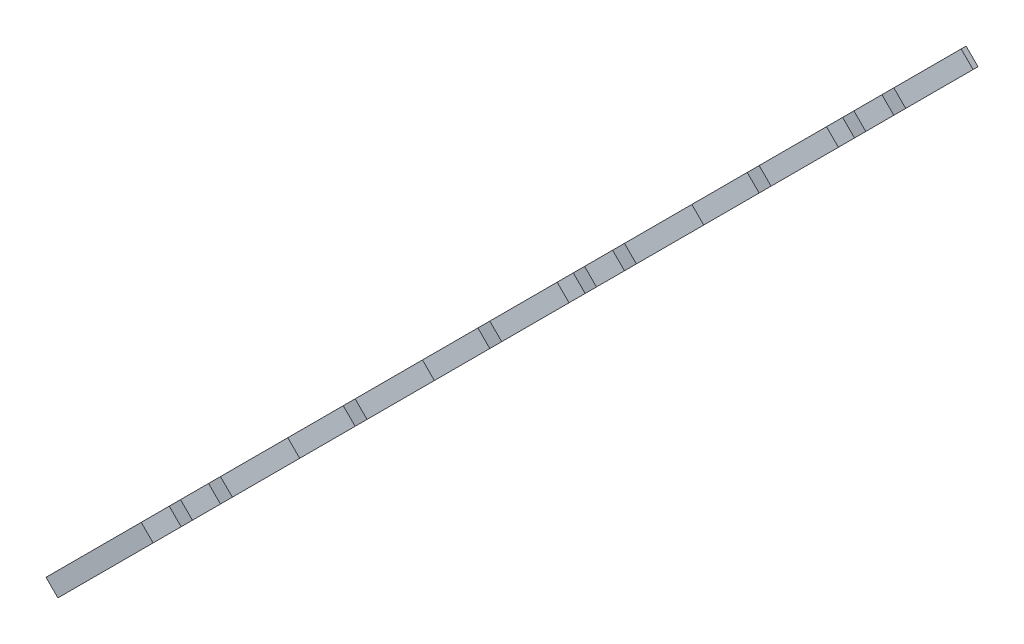
SolidWorks part; units mm, degrees
ref_plane "Front Plane" through (0, 0, 0) normal (0, 0, 1) x (1, 0, 0)
ref_plane "Top Plane" through (0, 0, 0) normal (0, 1, 0) x (1, 0, 0)
ref_plane "Right Plane" through (0, 0, 0) normal (1, 0, 0) x (0, 0, -1)
sketch "Sketch1" plane through (0, 0, 0) normal (0, 0, 1) x (1, 0, 0)
  line L0 (91.6648, 29.3027) -> (52.5461, -9.816) construction
  line L2 (78.5772, 20.7053) -> (74.1015, 16.2295) construction
  line L3 (78.5917, 11.7394) -> (83.0674, 16.2151) construction
  line L4 (37.7171, 7.6839) -> (33.2269, 12.174)
  line L5 (37.7171, 7.6839) -> (73.6381, 43.6049)
  line L6 (33.2269, 12.174) -> (69.148, 48.095)
  line L7 (73.6381, 43.6049) -> (69.148, 48.095)
  line L8 (110.4572, 6.7859) -> (74.5361, -29.1352) construction
  line L9 (74.5361, -29.1352) -> (70.046, -24.645) construction
  line L10 (105.967, 11.276) -> (70.046, -24.645) construction
extrude "Boss-Extrude1" add sketch "Sketch1" along normal up to surface (304.8 mm away)
sketch "Sketch2" plane through (58.6215, 58.6215, 0) normal (0.7071, 0.7071, 0) x (0, 0, -1)
  line L0 (-304.8, -21.2367) -> (0, -21.2367) construction
  line L1 (-279.4, -21.2367) -> (-254, -21.2367)
  line L2 (-279.4, -21.2367) -> (-279.4, -14.8867)
  line L3 (-279.4, -14.8867) -> (-254, -14.8867)
  line L4 (-254, -21.2367) -> (-254, -14.8867)
  line L5 (-304.8, -14.8867) -> (0, -14.8867) construction
  dimension "D1" = 25.4
  dimension "D2" = 25.4
extrude "Boss-Extrude2" add sketch "Sketch2" along normal blind 6.35
pattern_linear "LPattern1" count 6 spacing 50.8 along (0, 0, -1) of "Boss-Extrude2"
sketch "Sketch3" plane through (15.0166, -15.0166, 0) normal (0.7071, -0.7071, 0) x (0, 0, -1)
  circle A0 centre (-273.3375, 57.5033) radius 2.8702
extrude "Cut-Extrude1" cut sketch "Sketch3" against normal up to surface (6.35 mm away) up to face at (68.6299, 47.5769, 155.3308)
sketch "Sketch4" plane through (0, 0, 0) normal (0, 0, -1) x (-1, 0, 0)
  line L0 (-33.2269, 12.174) -> (-37.7171, 7.6839)
  line L1 (-73.6381, 52.5852) -> (-33.2269, 12.174) construction
  line L2 (-37.7171, 7.6839) -> (-78.1282, 48.095) construction
  line L3 (-37.7171, 7.6839) -> (-46.6973, 16.6641)
  line L4 (-46.6973, 16.6641) -> (-42.2072, 21.1543)
  line L5 (-42.2072, 21.1543) -> (-33.2269, 12.174)
  dimension "D1" = 12.7
  dimension "D2" = 0
  dimension "D3" = 6.35
extrude "Boss-Extrude3" add sketch "Sketch4" along normal blind 6.35
pattern_linear "LPattern2" count 2 spacing 38.1 along (0.7071, 0.7071, 0) of "Boss-Extrude3"
sketch "Sketch5" plane through (10.5265, -10.5265, 0) normal (-0.7071, 0.7071, 0) x (0.7071, 0.7071, 0)
  line L0 (57.5033, -7.2251) -> (57.5033, -39.5117) construction
  line L1 (44.8033, 6.35) -> (44.8033, 0) construction
  line L2 (70.2033, 6.35) -> (70.2033, 0) construction
  line L3 (70.2033, 0) -> (44.8033, 0) construction
  line B0 (59.6369, 0) -> (55.3697, 0)
  line B1 (55.3697, -11.938) -> (53.0583, -11.938)
  line B2 (53.0583, -11.938) -> (53.0583, -8.763)
  line B3 (53.0583, -8.763) -> (55.3697, -8.763)
  line B4 (55.3697, -8.763) -> (55.3697, 0)
  line B5 (55.3697, -11.938) -> (55.3697, -15.24)
  line B6 (55.3697, -15.24) -> (59.6369, -15.24)
  line B7 (59.6369, -11.938) -> (59.6369, -15.24)
  line B8 (59.6369, -8.763) -> (59.6369, 0)
  line B9 (61.9483, -8.763) -> (59.6369, -8.763)
  line B10 (61.9483, -11.938) -> (61.9483, -8.763)
  line B11 (59.6369, -11.938) -> (61.9483, -11.938)
sketch_block_instance "TSlot-1"
sketch_block "TSlot" parameters "D1"=3.302, "D2"=3.175
extrude "Cut-Extrude2" cut sketch "Sketch5" against normal through all
sketch "Sketch6" plane through (10.5265, -10.5265, 0) normal (-0.7071, 0.7071, 0) x (0.7071, 0.7071, 0)
  line L0 (82.9033, -292.1) -> (47.6349, -292.1) construction
  line L1 (82.9033, -304.8) -> (82.9033, -279.4) construction
  line L2 (82.9033, -139.7) -> (53.7612, -139.7) construction
  line L3 (82.9033, -152.4) -> (82.9033, -127) construction
  line L4 (82.9033, -38.1) -> (53.7612, -38.1) construction
  line L5 (82.9033, -50.8) -> (82.9033, -25.4) construction
  line L6 (89.2533, -25.4) -> (82.9033, -25.4) construction
  line L7 (89.2533, -50.8) -> (82.9033, -50.8) construction
  line L8 (89.2533, -127) -> (82.9033, -127) construction
  line L9 (89.2533, -152.4) -> (82.9033, -152.4) construction
  line L10 (89.2533, -279.4) -> (82.9033, -279.4) construction
  line L11 (32.1033, -304.8) -> (82.9033, -304.8) construction
  line B0 (82.9033, -294.2336) -> (82.9033, -289.9664)
  line B1 (70.9653, -289.9664) -> (70.9653, -287.655)
  line B2 (70.9653, -287.655) -> (74.1403, -287.655)
  line B3 (74.1403, -287.655) -> (74.1403, -289.9664)
  line B4 (74.1403, -289.9664) -> (82.9033, -289.9664)
  line B5 (70.9653, -289.9664) -> (67.6633, -289.9664)
  line B6 (67.6633, -289.9664) -> (67.6633, -294.2336)
  line B7 (70.9653, -294.2336) -> (67.6633, -294.2336)
  line B8 (74.1403, -294.2336) -> (82.9033, -294.2336)
  line B9 (74.1403, -296.545) -> (74.1403, -294.2336)
  line B10 (70.9653, -296.545) -> (74.1403, -296.545)
  line B11 (70.9653, -294.2336) -> (70.9653, -296.545)
  line B12 (82.9033, -141.8336) -> (82.9033, -137.5664)
  line B13 (70.9653, -137.5664) -> (70.9653, -135.255)
  line B14 (70.9653, -135.255) -> (74.1403, -135.255)
  line B15 (74.1403, -135.255) -> (74.1403, -137.5664)
  line B16 (74.1403, -137.5664) -> (82.9033, -137.5664)
  line B17 (70.9653, -137.5664) -> (67.6633, -137.5664)
  line B18 (67.6633, -137.5664) -> (67.6633, -141.8336)
  line B19 (70.9653, -141.8336) -> (67.6633, -141.8336)
  line B20 (74.1403, -141.8336) -> (82.9033, -141.8336)
  line B21 (74.1403, -144.145) -> (74.1403, -141.8336)
  line B22 (70.9653, -144.145) -> (74.1403, -144.145)
  line B23 (70.9653, -141.8336) -> (70.9653, -144.145)
  line B24 (82.9033, -40.2336) -> (82.9033, -35.9664)
  line B25 (70.9653, -35.9664) -> (70.9653, -33.655)
  line B26 (70.9653, -33.655) -> (74.1403, -33.655)
  line B27 (74.1403, -33.655) -> (74.1403, -35.9664)
  line B28 (74.1403, -35.9664) -> (82.9033, -35.9664)
  line B29 (70.9653, -35.9664) -> (67.6633, -35.9664)
  line B30 (67.6633, -35.9664) -> (67.6633, -40.2336)
  line B31 (70.9653, -40.2336) -> (67.6633, -40.2336)
  line B32 (74.1403, -40.2336) -> (82.9033, -40.2336)
  line B33 (74.1403, -42.545) -> (74.1403, -40.2336)
  line B34 (70.9653, -42.545) -> (74.1403, -42.545)
  line B35 (70.9653, -40.2336) -> (70.9653, -42.545)
sketch_block_instance "TSlot-2"
sketch_block_instance "TSlot-3"
sketch_block_instance "TSlot-4"
extrude "Cut-Extrude3" cut sketch "Sketch6" against normal through all
sketch "Sketch7" plane through (15.0166, -15.0166, 0) normal (0.7071, -0.7071, 0) x (-0.7071, -0.7071, 0)
  line L0 (-89.2533, -213.6951) -> (-82.9033, -217.9623) construction
  line L1 (-82.9033, -213.6951) -> (-89.2533, -217.9623) construction
  line L2 (-89.2533, -228.6) -> (-89.2533, -203.2) construction
  line L3 (-89.2533, -217.9623) -> (-82.9033, -217.9623) construction
  line L4 (-89.2533, -65.5623) -> (-82.9033, -61.2951) construction
  line L5 (-89.2533, -65.5623) -> (-82.9033, -65.5623) construction
  line L6 (-89.2533, -76.2) -> (-89.2533, -50.8) construction
  line L7 (-82.9033, -65.5623) -> (-89.2533, -61.2951) construction
  line L8 (-82.9033, -61.2951) -> (-89.2533, -61.2951) construction
  circle A0 centre (-86.0783, -215.8287) radius 2.0955
  circle A1 centre (-86.0783, -63.4287) radius 2.0955
  dimension "D1" = 4.191
extrude "Cut-Extrude4" cut sketch "Sketch7" against normal through all
sketch "Sketch8" plane through (10.5265, -10.5265, 0) normal (-0.7071, 0.7071, 0) x (0.7071, 0.7071, 0)
  line L0 (32.1033, -304.8) -> (32.1033, 6.35) construction
  line L1 (32.1033, -133.35) -> (51.1533, -133.35)
  line L2 (32.1033, -133.35) -> (32.1033, -196.85)
  line L3 (32.1033, -196.85) -> (51.1533, -196.85)
  line L4 (51.1533, -133.35) -> (51.1533, -196.85)
  line L5 (55.3697, 0) -> (44.8033, 0) construction
  dimension "D1" = 133.35
  dimension "D2" = 63.5
  dimension "D3" = 19.05
extrude "Cut-Extrude5" cut sketch "Sketch8" against normal through all
fillet "Fillet1" radius 3.81 4 edges at (48.9424, 23.3993, 196.85) (48.9424, 23.3993, 133.35) (35.472, 9.9289, 196.85) (35.472, 9.9289, 133.35)
